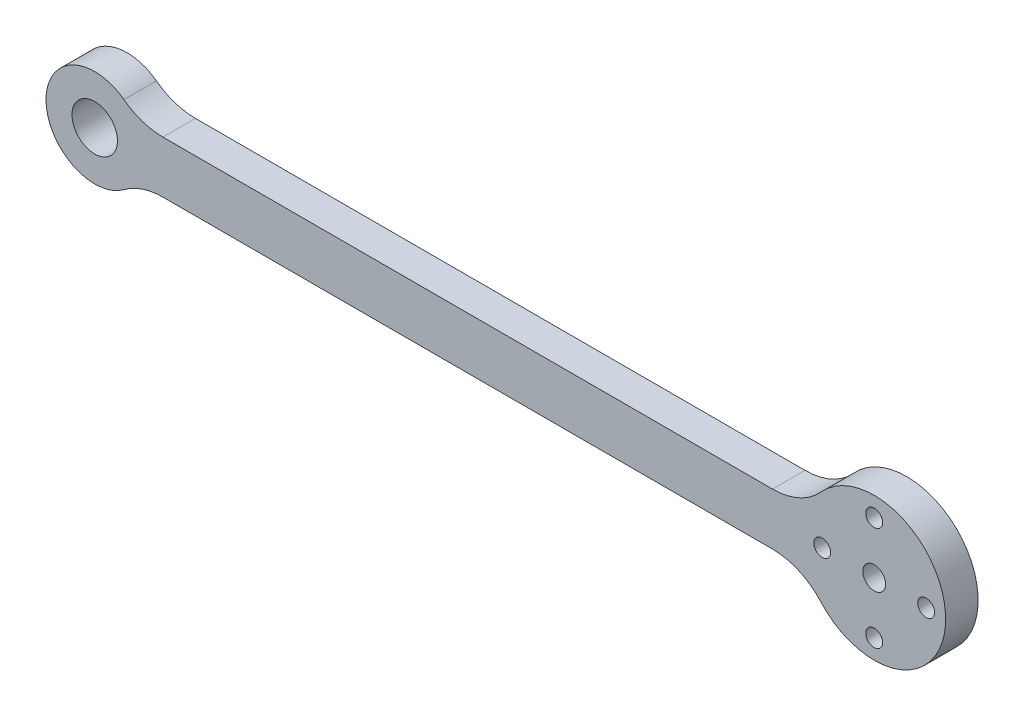
SolidWorks part; units mm, degrees
note: The reader was unsure of these and kept them because the rebuilt part matched: thickness of "Base-Flange1", "Sheet-Metal1".
ref_plane "Front Plane" through (0, 0, 0) normal (0, 0, 1) x (1, 0, 0)
ref_plane "Top Plane" through (0, 0, 0) normal (0, 1, 0) x (1, 0, 0)
ref_plane "Right Plane" through (0, 0, 0) normal (1, 0, 0) x (0, 0, -1)
sketch "Sketch1" plane through (0, 0, 0) normal (0, 0, 1) x (1, 0, 0)
  line L0 (112, 0) -> (128, 0) construction
  line L1 (6.3443, 4) -> (109.753, 4)
  line L2 (6.3443, 4) -> (6.3443, -4) construction
  line L3 (6.3443, -4) -> (109.753, -4)
  line L4 (109.753, 4) -> (109.753, -4) construction
  line L5 (120, -8) -> (120, 8) construction
  circle A0 centre (0, 0) radius 3.5
  arc A1 (6.3443, 4) -> (6.3443, -4) centre (0, 0) ccw
  arc A2 (109.753, -4) -> (109.753, 4) centre (120, 0) ccw
  arc A3 (109.753, 4) -> (109.753, -4) centre (120, 0) ccw construction
  arc A4 (6.3443, -4) -> (6.3443, 4) centre (0, 0) ccw construction
  circle A5 centre (112, 0) radius 1.3
  circle A6 centre (120, -8) radius 1.3
  circle A7 centre (128, 0) radius 1.3
  circle A8 centre (120, 8) radius 1.3
  circle A9 centre (120, 0) radius 1.75
  point P16 (120, 0)
  point P17 (120, 0)
  dimension "D1" = 7
  dimension "D2" = 15
  dimension "D4" = 22
  dimension "D6" = 2.6
  dimension "D8" = 3.5
  dimension "D3" = 120
  dimension "D5" = 8
  dimension "D7" = 16
base flange "Base-Flange1" sketch "Sketch1" thickness 5 reverse thickness direction no parameters "D1"=0.7366
fillet "Fillet1" radius 10 2 edges at (6.3443, 4, -2.5) (6.3443, -4, -2.5)
fillet "Fillet2" radius 10 2 edges at (109.753, 4, -2.5) (109.753, -4, -2.5)
sketch "Bend-Lines1" [suppressed] plane through (0, 0, 0) normal (0, 1, 0) x (1, 0, 0)
sketch "Bounding-Box1" [suppressed] plane through (0, 0, 0) normal (0, 1, 0) x (1, 0, 0)
sheet metal parameters "Sheet-Metal1" thickness 5 parameters "D1"=0.7366
flat pattern "Flat-Pattern1" [suppressed]
sketch "Bend-Lines2" plane through (0, 0, 0) normal (0, 1, 0) x (1, 0, 0)
sketch3d "Bounding-Box2" [suppressed]
  line L0 (-7.0738, -14.7126, 0) -> (131.3161, -10.6744, 0) construction
  line L1 (-7.7155, 7.2779, 0) -> (130.6744, 11.3161, 0) construction
  line L2 (-7.0738, -14.7126, 0) -> (-7.7155, 7.2779, 0) construction
  line L3 (131.3161, -10.6744, 0) -> (130.6744, 11.3161, 0) construction
